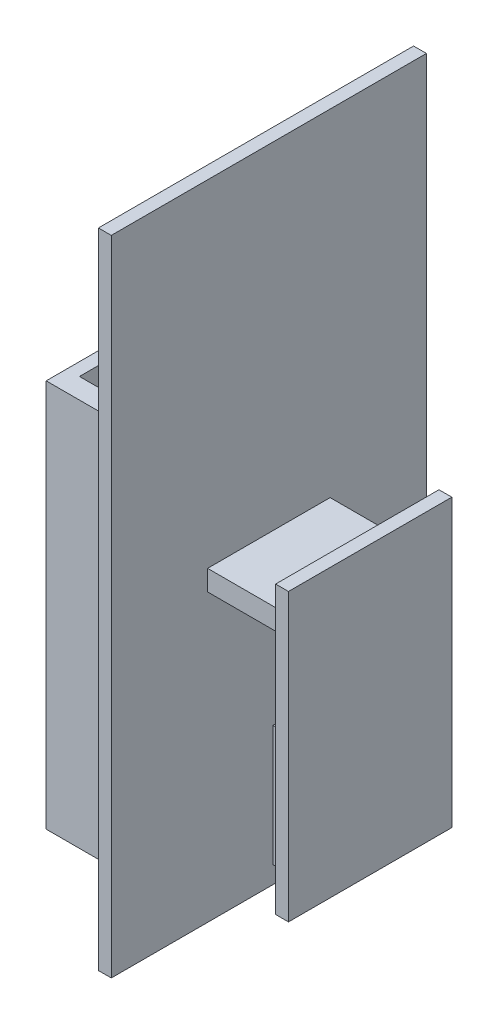
SolidWorks part; units mm, degrees
ref_plane "前基準面" through (0, 0, 0) normal (0, 0, 1) x (1, 0, 0)
ref_plane "上基準面" through (0, 0, 0) normal (0, 1, 0) x (1, 0, 0)
ref_plane "右基準面" through (0, 0, 0) normal (1, 0, 0) x (0, 0, -1)
sketch "草圖1" plane through (0, 0, 0) normal (1, 0, 0) x (0, 0, -1)
  line L0 (0, 0) -> (0, 40) construction
  line L1 (-19.6, -40) -> (19.6, -40)
  line L2 (-19.6, -40) -> (-19.6, 40)
  line L3 (-19.6, 40) -> (19.6, 40)
  line L4 (19.6, -40) -> (19.6, 40)
  line L5 (-19.6, -40) -> (19.6, 40) construction
  line L6 (-19.6, 40) -> (19.6, -40) construction
  line L7 (-12.7, 13.38) -> (12.7, 13.38)
  line L8 (-12.7, 13.38) -> (-12.7, -34.92)
  line L9 (-12.7, -34.92) -> (12.7, -34.92)
  line L10 (12.7, 13.38) -> (12.7, -34.92)
  line L11 (12.7, -34.92) -> (10.16, -34.92)
  line L12 (-12.7, 13.38) -> (-10.16, 13.38)
  line L13 (-12.7, 13.38) -> (-12.7, -34.92)
  line L14 (-12.7, -34.92) -> (-10.16, -34.92)
  line L15 (-10.16, 13.38) -> (-10.16, -34.92)
  line L16 (10.16, 13.38) -> (10.16, -34.92)
  line L17 (12.7, 13.38) -> (10.16, 13.38)
  line L18 (12.7, 13.38) -> (12.7, -34.92)
  line L20 (10.16, -32.38) -> (-10.16, -32.38)
  line L21 (10.16, -32.38) -> (10.16, 3.22)
  line L22 (10.16, 3.22) -> (-10.16, 3.22)
  line L23 (-10.16, -32.38) -> (-10.16, 3.22)
  line L24 (-7.62, -1.86) -> (7.62, -1.86)
  line L25 (-7.62, -1.86) -> (-7.62, -4.4)
  line L26 (-7.62, -4.4) -> (7.62, -4.4)
  line L27 (7.62, -1.86) -> (7.62, -4.4)
  line L28 (-7.5, -14.84) -> (7.5, -14.84)
  line L29 (-7.5, -14.84) -> (-7.5, -29.84)
  line L30 (-7.5, -29.84) -> (7.5, -29.84)
  line L31 (7.5, -14.84) -> (7.5, -29.84)
  line L36 (-3, -28.92) -> (3, -28.92)
  line L37 (-3, -28.92) -> (-3, -34.92)
  line L38 (-3, -34.92) -> (3, -34.92)
  line L39 (3, -28.92) -> (3, -34.92)
  point P0 (0, 0)
  point P13 (0, -34.92)
  dimension "D1" = 80
  dimension "D2" = 39.2
  dimension "D3" = 48.3
  dimension "D4" = 25.4
  dimension "D5" = 5.08
  dimension "D6" = 2.54
  dimension "D7" = 20.32
  dimension "D8" = 15.24
  dimension "D9" = 2.54
  dimension "D10" = 5.08
  dimension "D11" = 10.16
  dimension "D12" = 2.54
  dimension "D13" = 15
  dimension "D14" = 15
  dimension "D15" = 2.54
  dimension "D16" = 6
  dimension "D17" = 6
extrude "填料-伸長1" add sketch "草圖1" along normal blind 0.8 and the other way blind 0.8 contours L2 L3 L4 L1
extrude "填料-伸長2" add sketch "草圖1<3>" along normal blind 11.8 contours L25 L26 L27 L24
sketch "草圖1<3>" plane through (0, 0, 0) normal (1, 0, 0) x (0, 0, -1) same geometry as "草圖1"
sketch "草圖2" plane through (11.8, 0, 0) normal (1, 0, 0) x (0, 0, -1)
  line L0 (-12.7, -34.92) -> (12.7, -34.92) construction
  line L1 (12.7, 13.38) -> (12.7, -34.92) construction
  line L2 (12.7, -34.92) -> (10.16, -34.92) construction
  line L3 (10.16, 13.38) -> (10.16, -34.92) construction
  line L4 (7.62, -1.86) -> (-7.62, -1.86)
  line L5 (-7.62, -1.86) -> (-7.62, -4.4)
  line L6 (-7.62, -4.4) -> (7.62, -4.4)
  line L7 (7.62, -4.4) -> (7.62, -1.86)
  line L8 (7.62, -1.86) -> (-7.62, -1.86)
  line L9 (-7.62, -1.86) -> (-7.62, -4.4)
  line L10 (-7.62, -4.4) -> (7.62, -4.4)
  line L11 (7.62, -4.4) -> (7.62, -1.86)
  line L12 (12.7, 13.38) -> (10.16, 13.38) construction
  line L13 (12.7, 13.38) -> (12.7, -34.92) construction
  line L14 (-12.7, 13.38) -> (-12.7, -34.92) construction
  line L15 (-12.7, 13.38) -> (-12.7, -34.92) construction
  line L16 (-12.7, 13.38) -> (-10.16, 13.38) construction
  line L17 (-10.16, 13.38) -> (-10.16, -34.92) construction
  line L18 (-12.7, -34.92) -> (-10.16, -34.92) construction
  line L19 (-12.7, 13.38) -> (12.7, 13.38) construction
  line L20 (-19.6, -40) -> (19.6, -40) construction
  line L21 (19.6, -40) -> (19.6, 40) construction
  line L22 (-19.6, 40) -> (19.6, 40) construction
  line L23 (-19.6, -40) -> (-19.6, 40) construction
  line L24 (-7.5, -14.84) -> (7.5, -14.84) construction
  line L25 (7.5, -14.84) -> (7.5, -29.84) construction
  line L26 (-7.5, -29.84) -> (7.5, -29.84) construction
  line L27 (-7.5, -14.84) -> (-7.5, -29.84) construction
  line L28 (-7.62, -1.86) -> (7.62, -1.86) construction
  line L29 (7.62, -1.86) -> (7.62, -4.4) construction
  line L30 (-7.62, -4.4) -> (7.62, -4.4) construction
  line L31 (-7.62, -1.86) -> (-7.62, -4.4) construction
  line L32 (10.16, -32.38) -> (-10.16, -32.38) construction
  line L33 (-10.16, -32.38) -> (-10.16, 3.22) construction
  line L34 (10.16, 3.22) -> (-10.16, 3.22) construction
  line L35 (10.16, -32.38) -> (10.16, 3.22) construction
  line L36 (-3, -28.92) -> (3, -28.92) construction
  line L37 (-3, -28.92) -> (-3, -34.92) construction
  line L38 (-3, -34.92) -> (3, -34.92) construction
  line L39 (3, -28.92) -> (3, -34.92) construction
  line L40 (-12.7, -34.92) -> (12.7, -34.92)
  line L41 (12.7, 13.38) -> (12.7, -34.92)
  line L42 (12.7, -34.92) -> (10.16, -34.92)
  line L43 (10.16, 13.38) -> (10.16, -34.92)
  line L44 (12.7, 13.38) -> (10.16, 13.38)
  line L45 (12.7, 13.38) -> (12.7, -34.92)
  line L46 (-12.7, 13.38) -> (-12.7, -34.92)
  line L47 (-12.7, 13.38) -> (-12.7, -34.92)
  line L48 (-12.7, 13.38) -> (-10.16, 13.38)
  line L49 (-10.16, 13.38) -> (-10.16, -34.92)
  line L50 (-12.7, -34.92) -> (-10.16, -34.92)
  line L51 (-12.7, 13.38) -> (12.7, 13.38)
  line L52 (-19.6, -40) -> (19.6, -40)
  line L53 (19.6, -40) -> (19.6, 40)
  line L54 (-19.6, 40) -> (19.6, 40)
  line L55 (-19.6, -40) -> (-19.6, 40)
  line L56 (-7.5, -14.84) -> (7.5, -14.84)
  line L57 (7.5, -14.84) -> (7.5, -29.84)
  line L58 (-7.5, -29.84) -> (7.5, -29.84)
  line L59 (-7.5, -14.84) -> (-7.5, -29.84)
  line L60 (-7.62, -1.86) -> (7.62, -1.86)
  line L61 (7.62, -1.86) -> (7.62, -4.4)
  line L62 (-7.62, -4.4) -> (7.62, -4.4)
  line L63 (-7.62, -1.86) -> (-7.62, -4.4)
  line L64 (10.16, -32.38) -> (-10.16, -32.38)
  line L65 (-10.16, -32.38) -> (-10.16, 3.22)
  line L66 (10.16, 3.22) -> (-10.16, 3.22)
  line L67 (10.16, -32.38) -> (10.16, 3.22)
  line L68 (-3, -28.92) -> (3, -28.92)
  line L69 (-3, -28.92) -> (-3, -34.92)
  line L70 (-3, -34.92) -> (3, -34.92)
  line L71 (3, -28.92) -> (3, -34.92)
  line M13 (7.62, -1.86) -> (-7.62, -1.86)
  line M14 (-7.62, -1.86) -> (-7.62, -4.4)
  line M15 (-7.62, -4.4) -> (7.62, -4.4)
  line M16 (7.62, -4.4) -> (7.62, -1.86)
  dimension "D1" = 0
extrude "填料-伸長3" add sketch "草圖2" along normal blind 1.6 contours L58 L71 L64 L43 L66 L49 L69 L59 L56 L57 M13 M16 M15 M14 | L71 L58 L69 L64 | M16 M13 M14 M15 | L68 L71 L58 L57 L56 L59 L69 | L71 L68 L69 L58 region at (11.8, -3.13, 0) region at (11.8, -11.0819, 0) region at (11.8, -31.11, 0) region at (11.8, -29.38, 0) region at (11.8, -22.1629, 0)
extrude "填料-伸長4" add sketch "草圖2<3>" against normal blind 3 contours L59 L58 L57 L56
sketch "草圖2<3>" plane through (11.8, 0, 0) normal (1, 0, 0) x (0, 0, -1) same geometry as "草圖2"
extrude "填料-伸長6" add sketch "草圖1<4>" against normal blind 12.6 contours L15 L7 L8 L9 | L7 L16 L9 L10 region at (0, -10.77, 11.43) region at (0, -10.77, -11.43)
sketch "草圖1<4>" plane through (0, 0, 0) normal (1, 0, 0) x (0, 0, -1) same geometry as "草圖1"
sketch "草圖3" plane through (-12.6, 0, 0) normal (-1, 0, 0) x (0, 0, 1)
  line L0 (12.7, -34.92) -> (-12.7, -34.92) construction
  line L1 (-12.7, 13.38) -> (-12.7, -34.92) construction
  line L2 (-12.7, -34.92) -> (-10.16, -34.92) construction
  line L3 (-10.16, 13.38) -> (-10.16, -34.92) construction
  line L4 (-10.16, 13.38) -> (-12.7, 13.38)
  line L5 (-12.7, 13.38) -> (-12.7, -34.92)
  line L6 (-12.7, -34.92) -> (-10.16, -34.92)
  line L7 (-10.16, -34.92) -> (-10.16, 13.38)
  line L8 (-10.16, 13.38) -> (-12.7, 13.38)
  line L9 (-12.7, 13.38) -> (-12.7, -34.92)
  line L10 (-12.7, -34.92) -> (-10.16, -34.92)
  line L11 (-10.16, -34.92) -> (-10.16, 13.38)
  line L12 (-12.7, 13.38) -> (-10.16, 13.38) construction
  line L13 (-12.7, 13.38) -> (-12.7, -34.92) construction
  line L14 (12.7, 13.38) -> (12.7, -34.92) construction
  line L15 (12.7, 13.38) -> (12.7, -34.92) construction
  line L16 (12.7, 13.38) -> (10.16, 13.38) construction
  line L17 (10.16, 13.38) -> (10.16, -34.92) construction
  line L18 (12.7, -34.92) -> (10.16, -34.92) construction
  line L19 (12.7, 13.38) -> (-12.7, 13.38) construction
  line L20 (19.6, -40) -> (-19.6, -40) construction
  line L21 (-19.6, -40) -> (-19.6, 40) construction
  line L22 (19.6, 40) -> (-19.6, 40) construction
  line L23 (19.6, -40) -> (19.6, 40) construction
  line L24 (7.5, -14.84) -> (-7.5, -14.84) construction
  line L25 (-7.5, -14.84) -> (-7.5, -29.84) construction
  line L26 (7.5, -29.84) -> (-7.5, -29.84) construction
  line L27 (7.5, -14.84) -> (7.5, -29.84) construction
  line L28 (7.62, -1.86) -> (-7.62, -1.86) construction
  line L29 (-7.62, -1.86) -> (-7.62, -4.4) construction
  line L30 (7.62, -4.4) -> (-7.62, -4.4) construction
  line L31 (7.62, -1.86) -> (7.62, -4.4) construction
  line L32 (-10.16, -32.38) -> (10.16, -32.38) construction
  line L33 (10.16, -32.38) -> (10.16, 3.22) construction
  line L34 (-10.16, 3.22) -> (10.16, 3.22) construction
  line L35 (-10.16, -32.38) -> (-10.16, 3.22) construction
  line L36 (3, -28.92) -> (-3, -28.92) construction
  line L37 (3, -28.92) -> (3, -34.92) construction
  line L38 (3, -34.92) -> (-3, -34.92) construction
  line L39 (-3, -28.92) -> (-3, -34.92) construction
  line L40 (12.7, -34.92) -> (-12.7, -34.92)
  line L41 (-12.7, 13.38) -> (-12.7, -34.92)
  line L42 (-12.7, -34.92) -> (-10.16, -34.92)
  line L43 (-10.16, 13.38) -> (-10.16, -34.92)
  line L44 (-12.7, 13.38) -> (-10.16, 13.38)
  line L45 (-12.7, 13.38) -> (-12.7, -34.92)
  line L46 (12.7, 13.38) -> (12.7, -34.92)
  line L47 (12.7, 13.38) -> (12.7, -34.92)
  line L48 (12.7, 13.38) -> (10.16, 13.38)
  line L49 (10.16, 13.38) -> (10.16, -34.92)
  line L50 (12.7, -34.92) -> (10.16, -34.92)
  line L51 (12.7, 13.38) -> (-12.7, 13.38)
  line L52 (19.6, -40) -> (-19.6, -40)
  line L53 (-19.6, -40) -> (-19.6, 40)
  line L54 (19.6, 40) -> (-19.6, 40)
  line L55 (19.6, -40) -> (19.6, 40)
  line L56 (7.5, -14.84) -> (-7.5, -14.84)
  line L57 (-7.5, -14.84) -> (-7.5, -29.84)
  line L58 (7.5, -29.84) -> (-7.5, -29.84)
  line L59 (7.5, -14.84) -> (7.5, -29.84)
  line L60 (7.62, -1.86) -> (-7.62, -1.86)
  line L61 (-7.62, -1.86) -> (-7.62, -4.4)
  line L62 (7.62, -4.4) -> (-7.62, -4.4)
  line L63 (7.62, -1.86) -> (7.62, -4.4)
  line L64 (-10.16, -32.38) -> (10.16, -32.38)
  line L65 (10.16, -32.38) -> (10.16, 3.22)
  line L66 (-10.16, 3.22) -> (10.16, 3.22)
  line L67 (-10.16, -32.38) -> (-10.16, 3.22)
  line L68 (3, -28.92) -> (-3, -28.92)
  line L69 (3, -28.92) -> (3, -34.92)
  line L70 (3, -34.92) -> (-3, -34.92)
  line L71 (-3, -28.92) -> (-3, -34.92)
  line L72 (12.7, -34.92) -> (-12.7, -34.92)
  line L73 (-12.7, 13.38) -> (-12.7, -34.92)
  line L74 (-12.7, -34.92) -> (-10.16, -34.92)
  line L75 (-10.16, 13.38) -> (-10.16, -34.92)
  line L76 (-12.7, 13.38) -> (-10.16, 13.38)
  line L77 (-12.7, 13.38) -> (-12.7, -34.92)
  line L78 (12.7, 13.38) -> (12.7, -34.92)
  line L79 (12.7, 13.38) -> (12.7, -34.92)
  line L80 (12.7, 13.38) -> (10.16, 13.38)
  line L81 (10.16, 13.38) -> (10.16, -34.92)
  line L82 (12.7, -34.92) -> (10.16, -34.92)
  line L83 (12.7, 13.38) -> (-12.7, 13.38)
  line L84 (19.6, -40) -> (-19.6, -40)
  line L85 (-19.6, -40) -> (-19.6, 40)
  line L86 (19.6, 40) -> (-19.6, 40)
  line L87 (19.6, -40) -> (19.6, 40)
  line L88 (7.5, -14.84) -> (-7.5, -14.84)
  line L89 (-7.5, -14.84) -> (-7.5, -29.84)
  line L90 (7.5, -29.84) -> (-7.5, -29.84)
  line L91 (7.5, -14.84) -> (7.5, -29.84)
  line L92 (7.62, -1.86) -> (-7.62, -1.86)
  line L93 (-7.62, -1.86) -> (-7.62, -4.4)
  line L94 (7.62, -4.4) -> (-7.62, -4.4)
  line L95 (7.62, -1.86) -> (7.62, -4.4)
  line L96 (-10.16, -32.38) -> (10.16, -32.38)
  line L97 (10.16, -32.38) -> (10.16, 3.22)
  line L98 (-10.16, 3.22) -> (10.16, 3.22)
  line L99 (-10.16, -32.38) -> (-10.16, 3.22)
  line L100 (3, -28.92) -> (-3, -28.92)
  line L101 (3, -28.92) -> (3, -34.92)
  line L102 (3, -34.92) -> (-3, -34.92)
  line L103 (-3, -28.92) -> (-3, -34.92)
  line M9 (-10.16, 13.38) -> (-12.7, 13.38)
  line M10 (-12.7, 13.38) -> (-12.7, -34.92)
  line M11 (-12.7, -34.92) -> (-10.16, -34.92)
  line M12 (-10.16, -34.92) -> (-10.16, 13.38)
  dimension "D1" = 0
extrude "填料-伸長7" add sketch "草圖3" along normal blind 1.6 contours L43 M12 M9 M10 M11 | L66 L49 L51 M12 | L48 L49 L40 L46 | L71 L58 L57 L56 L59 L69 L64 L49 L66 L43 L60 L63 L62 L61 | L63 L60 L61 L62 | L71 L68 L69 L58 L59 L56 L57 | L71 L64 L40 M12 | L64 L69 L40 L49 region at (-12.6, -10.77, -11.43) region at (-12.6, 8.3, 0) region at (-12.6, -11.0819, 0) region at (-12.6, -10.77, 11.43) region at (-12.6, -33.65, -6.58) region at (-12.6, -33.65, 6.58) region at (-12.6, -22.1629, 0) region at (-12.6, -3.13, 0)
extrude "填料-伸長8" add sketch "草圖3<3>" along normal blind 4.6 contours L64 L71 L40 L69 | L58 L71 L64 L69 | L68 L71 L58 L69 region at (-12.6, -31.11, 0) region at (-12.6, -33.65, 0) region at (-12.6, -29.38, 0)
sketch "草圖3<3>" plane through (-12.6, 0, 0) normal (-1, 0, 0) x (0, 0, 1) same geometry as "草圖3"
